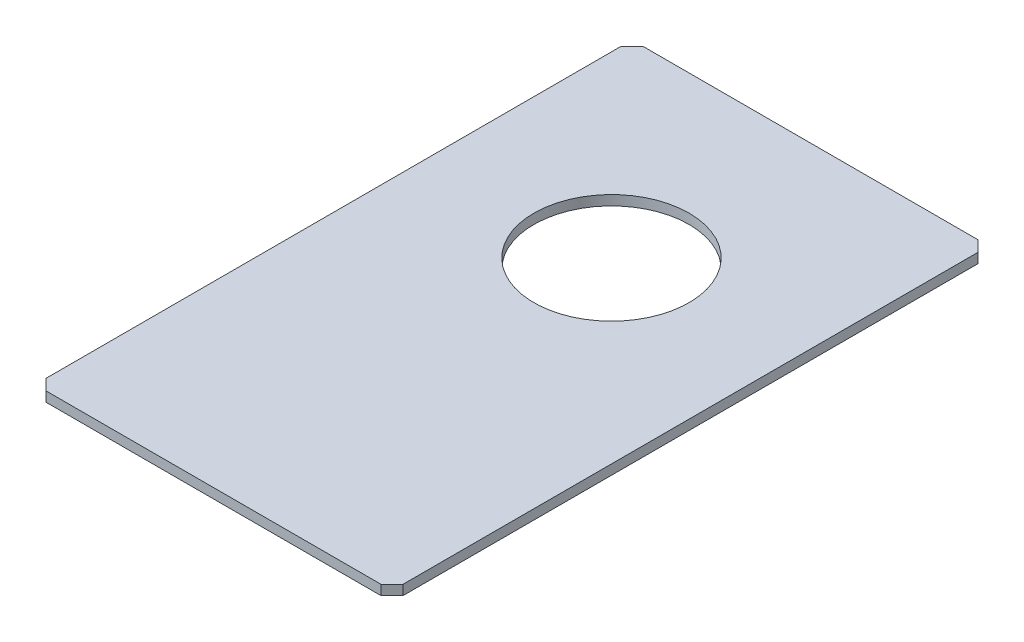
SolidWorks part; units mm, degrees
ref_plane "Front Plane" through (0, 0, 0) normal (0, 0, 1) x (1, 0, 0)
ref_plane "Top Plane" through (0, 0, 0) normal (0, 1, 0) x (1, 0, 0)
ref_plane "Right Plane" through (0, 0, 0) normal (1, 0, 0) x (0, 0, -1)
sketch "Sketch1" plane through (0, 0, 0) normal (0, 1, 0) x (1, 0, 0)
  line L1 (57.5, -96.1727) -> (-57.5, -96.1727)
  line L2 (57.5, -96.1727) -> (57.5, 96.1727)
  line L3 (57.5, 96.1727) -> (-57.5, 96.1727)
  line L4 (-57.5, -96.1727) -> (-57.5, 96.1727)
  line L5 (57.5, -96.1727) -> (-57.5, 96.1727) construction
  line L6 (57.5, 96.1727) -> (-57.5, -96.1727) construction
  point P0 (0, 0)
  dimension "D1" = 115
  dimension "D2" = 192.3454
extrude "Boss-Extrude1" add sketch "Sketch1" along normal blind 3.175
chamfer "Chamfer1" distance 3.5 angle 45 4 edges at (57.5, 1.5875, -96.1727) (-57.5, 1.5875, -96.1727) (-57.5, 1.5875, 96.1727) (57.5, 1.5875, 96.1727)
sketch "Sketch2" plane through (0, 0, 0) normal (0, -1, 0) x (1, 0, 0)
  line L0 (0, -96.1727) -> (0, -32.0576) construction
  line L1 (54, -96.1727) -> (-54, -96.1727) construction
  line L2 (0, -32.0576) -> (0, 32.0576) construction
  line L3 (0, 32.0576) -> (0, 96.1727) construction
  line L4 (-54, 96.1727) -> (54, 96.1727) construction
  circle A0 centre (0, -32.0576) radius 25
  dimension "D1" = 50
extrude "Cut-Extrude1" cut sketch "Sketch2" against normal through all
